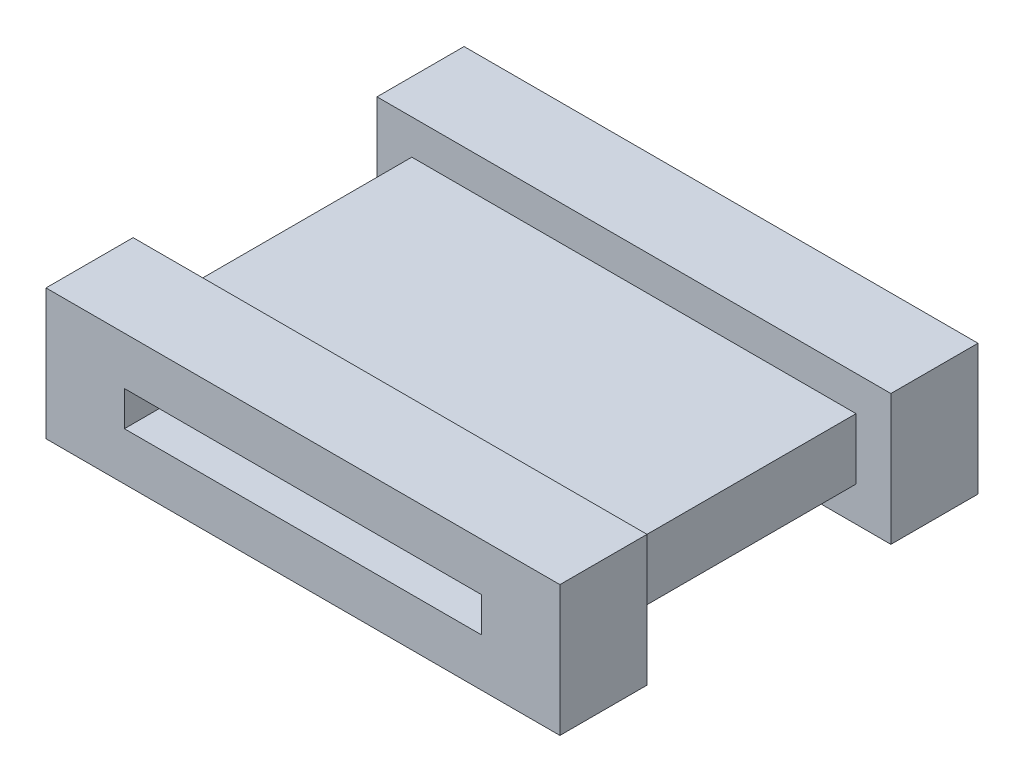
SolidWorks part; units mm, degrees
ref_plane "Front Plane" through (0, 0, 0) normal (0, 0, 1) x (1, 0, 0)
ref_plane "Top Plane" through (0, 0, 0) normal (0, 1, 0) x (1, 0, 0)
ref_plane "Right Plane" through (0, 0, 0) normal (1, 0, 0) x (0, 0, -1)
sketch "Sketch1" plane through (0, 0, 0) normal (0, 1, 0) x (1, 0, 0)
  line L1 (-29.5, -24) -> (29.5, -24)
  line L2 (-29.5, -24) -> (-29.5, 24)
  line L3 (-29.5, 24) -> (29.5, 24)
  line L4 (29.5, -24) -> (29.5, 24)
  line L5 (-29.5, -24) -> (29.5, 24) construction
  line L6 (-29.5, 24) -> (29.5, -24) construction
  point P0 (0, 0)
  dimension "D1" = 59
  dimension "D2" = 48
extrude "Boss-Extrude1" add sketch "Sketch1" along normal blind 7.5 and the other way blind 7.5
sketch "Sketch2" plane through (0, 0, 24) normal (0, 0, 1) x (1, 0, 0)
  line L0 (0, 7.5) -> (0, -7.5) construction
  line L1 (-20.5, 2) -> (20.5, 2)
  line L2 (-20.5, 2) -> (-20.5, -2)
  line L3 (-20.5, -2) -> (20.5, -2)
  line L4 (20.5, 2) -> (20.5, -2)
  line L5 (-20.5, 2) -> (20.5, -2) construction
  line L6 (-20.5, -2) -> (20.5, 2) construction
  line L7 (-29.5, 7.5) -> (29.5, 7.5) construction
  line L8 (-29.5, -7.5) -> (29.5, -7.5) construction
  point P0 (0, 0)
  dimension "D1" = 41
  dimension "D2" = 4
extrude "Cut-Extrude1" cut sketch "Sketch2" against normal through all
sketch "Sketch3" plane through (0, 7.5, 0) normal (0, 1, 0) x (1, 0, 0)
  line L13 (29.5, -24) -> (29.5, 24) construction
  line L14 (-29.5, 24) -> (-29.5, -24) construction
  line L18 (-29.5, 14) -> (-29.5, -14)
  line L19 (29.5, -14) -> (29.5, 14)
  line L20 (-29.5, -14) -> (29.5, -14)
  line L21 (29.5, 14) -> (-29.5, 14)
extrude "Cut-Extrude2" cut sketch "Sketch3" against normal blind 4
sketch "Sketch4" plane through (-29.5, 0, 0) normal (-1, 0, 0) x (0, 0, 1)
  line L0 (-24, -7.5) -> (24, -7.5) construction
  line L1 (-14, 3.5) -> (14, 3.5)
  line L2 (-14, 3.5) -> (-14, -7.5)
  line L3 (-14, -7.5) -> (14, -7.5)
  line L4 (14, 3.5) -> (14, -7.5)
  line L5 (14, 3.5) -> (14, 7.5) construction
extrude "Cut-Extrude3" cut sketch "Sketch4" against normal blind 4
mirror "Mirror1" about plane through (0, 0, 0) normal (1, 0, 0) of "Cut-Extrude3"
mirror "Mirror2" about plane through (0, 0, 0) normal (0, 1, 0) of "Cut-Extrude2"
